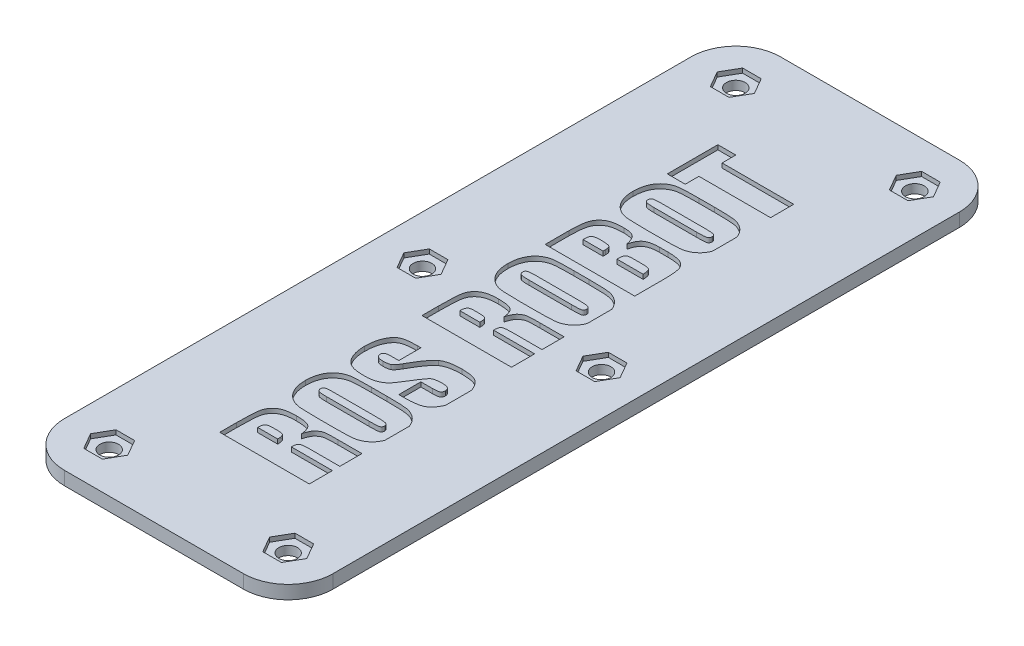
SolidWorks part; units mm, degrees
ref_plane "Front Plane" through (0, 0, 0) normal (0, 0, 1) x (1, 0, 0)
ref_plane "Top Plane" through (0, 0, 0) normal (0, 1, 0) x (1, 0, 0)
ref_plane "Right Plane" through (0, 0, 0) normal (1, 0, 0) x (0, 0, -1)
sketch "Sketch1" plane through (0, 0, 0) normal (0, 1, 0) x (1, 0, 0)
  line L1 (-30, 80) -> (30, 80)
  line L2 (-30, 80) -> (-30, -80)
  line L3 (-30, -80) -> (30, -80)
  line L4 (30, 80) -> (30, -80)
  line L5 (-30, 80) -> (30, -80) construction
  line L6 (-30, -80) -> (30, 80) construction
  point P0 (0, 0)
  dimension "D1" = 60
  dimension "D2" = 160
extrude "Boss-Extrude1" add sketch "Sketch1" along normal blind 3
sketch "Sketch2" plane through (0, 3, 0) normal (0, 1, 0) x (1, 0, 0)
  line L0 (-30, -80) -> (30, -80) construction
  line L2 (-30, 80) -> (-30, -80) construction
  circle A0 centre (-20, -70) radius 2.09
  circle A1 centre (-20, 0) radius 2.09
  circle A2 centre (-20, 70) radius 2.09
  dimension "D1" = 4.18
  dimension "D2" = 70
  dimension "D3" = 70
  dimension "D4" = 10
  dimension "D5" = 10
extrude "Cut-Extrude1" cut sketch "Sketch2" against normal through all
mirror "Mirror1" about plane through (0, 0, 0) normal (1, 0, 0) of "Cut-Extrude1"
sketch "Sketch3" plane through (0, 3, 0) normal (0, 1, 0) x (1, 0, 0)
  line L0 (10, -60) -> (10, 60)
  line L1 (-30, 80) -> (-30, -80) construction
  line L2 (-10, -55.2941) -> (-10, -51.5662)
  line L3 (4.6581, -43.5294) -> (10, -43.5294)
  line L4 (10, -43.5294) -> (10, -48.4706)
  line L5 (10, -48.4706) -> (3.2353, -48.4706)
  line L6 (0.8235, -50.1176) -> (10, -50.1176)
  line L7 (10, -50.1176) -> (10, -55.2941)
  line L8 (10, -55.2941) -> (-10, -55.2941)
  line L9 (-6.7059, -50.1176) -> (-2.2353, -50.1176)
  line L10 (-4.0478, -48.4706) -> (-5.1544, -48.4706)
  line L11 (1.7206, -41.6471) -> (-1.7206, -41.6471)
  line L12 (-1.7206, -29.6471) -> (1.7206, -29.6471)
  line L13 (-4.9596, -36.4706) -> (4.5662, -36.4706)
  line L14 (4.4154, -34.8235) -> (-4.9596, -34.8235)
  line L15 (-3.8824, -16.4706) -> (-3.8824, -21.4118)
  line L16 (-3.8824, -21.4118) -> (-5.4632, -21.4118)
  line L17 (4.0478, -28) -> (2.7059, -28)
  line L18 (2.7059, -28) -> (2.7059, -23.0588)
  line L19 (2.7059, -23.0588) -> (5.2978, -23.0588)
  line L20 (-4.6875, -16.4706) -> (-3.8824, -16.4706)
  line L21 (-10, -10.1176) -> (-10, -6.3897)
  line L22 (4.6581, 1.6471) -> (10, 1.6471)
  line L23 (10, 1.6471) -> (10, -3.2941)
  line L24 (10, -3.2941) -> (3.2353, -3.2941)
  line L25 (0.8235, -4.9412) -> (10, -4.9412)
  line L26 (10, -4.9412) -> (10, -10.1176)
  line L27 (10, -10.1176) -> (-10, -10.1176)
  line L28 (-6.7059, -4.9412) -> (-2.2353, -4.9412)
  line L29 (-4.0478, -3.2941) -> (-5.1544, -3.2941)
  line L30 (1.7206, 3.5294) -> (-1.7206, 3.5294)
  line L31 (-1.7206, 15.5294) -> (1.7206, 15.5294)
  line L32 (-4.9596, 8.7059) -> (4.5662, 8.7059)
  line L33 (4.4154, 10.3529) -> (-4.9596, 10.3529)
  line L34 (-10, 17.4118) -> (-10, 22.7169)
  line L35 (3.364, 29.6471) -> (5.2426, 29.6471)
  line L36 (10, 23.4926) -> (10, 17.4118)
  line L37 (10, 17.4118) -> (-10, 17.4118)
  line L38 (-6.7059, 22.5882) -> (-2.2353, 22.5882)
  line L39 (0.8235, 22.5882) -> (6.7059, 22.5882)
  line L40 (4.7463, 24.4706) -> (2.7831, 24.4706)
  line L41 (1.7206, 31.5294) -> (-1.7206, 31.5294)
  line L42 (-1.7206, 43.5294) -> (1.7206, 43.5294)
  line L43 (-4.9596, 36.7059) -> (4.5662, 36.7059)
  line L44 (4.4154, 38.3529) -> (-4.9596, 38.3529)
  line L45 (-10, 56) -> (-6, 56)
  line L46 (-6, 56) -> (-6, 52.9412)
  line L47 (-6, 52.9412) -> (10, 52.9412)
  line L48 (10, 52.9412) -> (10, 47.7647)
  line L49 (10, 47.7647) -> (-6, 47.7647)
  line L50 (-6, 47.7647) -> (-6, 44.7059)
  line L51 (-6, 44.7059) -> (-10, 44.7059)
  line L52 (-10, 44.7059) -> (-10, 56)
  spline S0 degree 3 poles (-10, -51.5662) (-10.0021, -50.9938) (-9.9925, -50.1738) (-9.9618, -49.131) (-9.9343, -48.4616) (-9.8938, -47.8671) (-9.8469, -47.3485) (-9.7938, -46.9053) (-9.7279, -46.5265) (-9.6422, -46.1927) (-9.5296, -45.8846) (-9.3956, -45.5898) (-9.2282, -45.3117) (-9.0316, -45.0523) (-8.8156, -44.8023) (-8.5646, -44.5748) (-8.2904, -44.3559) (-7.9777, -44.158) (-7.6226, -43.9907) (-7.2263, -43.847) (-6.7869, -43.7305) (-6.3051, -43.6403) (-5.579, -43.5478) (-5.0099, -43.5348) (-4.6176, -43.5294) knots 0 0 0 0 0.148881 0.213303 0.271377 0.323138 0.368276 0.406827 0.439217 0.468212 0.496346 0.524443 0.552325 0.580569 0.609028 0.638128 0.668547 0.700209 0.734143 0.770448 0.80973 0.852244 0.897872 1 1 1 1
  spline S1 degree 3 poles (-4.6176, -43.5294) (-4.2653, -43.5236) (-3.7599, -43.5474) (-3.1182, -43.6025) (-2.7075, -43.671) (-2.3432, -43.7491) (-2.0238, -43.8459) (-1.7543, -43.9676) (-1.5246, -44.1057) (-1.3304, -44.2743) (-1.1605, -44.4757) (-1.0104, -44.7121) (-0.8806, -44.9835) (-0.7776, -45.291) (-0.6464, -45.7633) (-0.5975, -46.1443) (-0.5735, -46.4081) knots 0 0 0 0 0.183844 0.264214 0.336185 0.401092 0.458783 0.510057 0.555172 0.598283 0.643683 0.692329 0.744143 0.800414 0.861431 1 1 1 1
  spline S2 degree 3 poles (-0.5735, -46.4081) (-0.5082, -46.1692) (-0.4158, -45.8227) (-0.2536, -45.3924) (-0.1242, -45.1174) (0.0082, -44.8722) (0.1462, -44.6567) (0.2982, -44.4752) (0.5056, -44.2791) (0.7695, -44.0853) (1.0739, -43.8901) (1.3668, -43.7472) (1.6163, -43.6653) (1.8438, -43.6284) (2.0703, -43.5981) (2.3577, -43.579) (2.7033, -43.5604) (3.1078, -43.5466) (3.7658, -43.5296) (4.2893, -43.5348) (4.6581, -43.5294) knots 0 0 0 0 0.11021 0.159198 0.204304 0.245276 0.283065 0.317885 0.350264 0.409778 0.463156 0.510931 0.554366 0.579275 0.613344 0.655979 0.70728 0.767268 0.835956 1 1 1 1
  spline S3 degree 3 poles (3.2353, -48.4706) (2.989, -48.4726) (2.6391, -48.4726) (2.1993, -48.5048) (1.9269, -48.5332) (1.6924, -48.5693) (1.4957, -48.6105) (1.339, -48.6657) (1.2146, -48.7289) (1.114, -48.8112) (1.0393, -48.9233) (0.9667, -49.0542) (0.9194, -49.2179) (0.8733, -49.4037) (0.8356, -49.7073) (0.824, -49.9481) (0.8235, -50.1176) knots 0 0 0 0 0.208735 0.296167 0.373443 0.440695 0.497113 0.543415 0.581035 0.614932 0.652106 0.694368 0.741317 0.795712 0.856499 1 1 1 1
  spline S4 degree 3 poles (-2.2353, -50.1176) (-2.241, -49.859) (-2.2449, -49.4942) (-2.3595, -49.0703) (-2.4455, -48.8674) (-2.5571, -48.7457) (-2.6702, -48.6674) (-2.8204, -48.6082) (-3.0015, -48.5571) (-3.2158, -48.5182) (-3.5672, -48.4758) (-3.8494, -48.4762) (-4.0478, -48.4706) knots 0 0 0 0 0.26299 0.361623 0.442867 0.481356 0.526611 0.580322 0.643299 0.716254 0.799641 1 1 1 1
  spline S5 degree 3 poles (-5.1544, -48.4706) (-5.4183, -48.4732) (-5.7882, -48.4915) (-6.209, -48.649) (-6.422, -48.8134) (-6.5523, -49.0502) (-6.6913, -49.4796) (-6.7008, -49.8538) (-6.7059, -50.1176) knots 0 0 0 0 0.296724 0.405999 0.497474 0.590179 0.702697 1 1 1 1
  spline S6 degree 3 poles (1.7206, -29.6471) (2.1887, -29.6516) (2.8628, -29.6489) (3.7244, -29.6629) (4.2868, -29.6838) (4.7956, -29.6992) (5.249, -29.7256) (5.6474, -29.7548) (6.1016, -29.7961) (6.625, -29.8819) (7.2194, -30.0688) (7.7848, -30.3319) (8.3184, -30.6676) (8.8126, -31.0692) (9.2459, -31.5466) (9.6203, -32.0876) (9.9272, -32.6949) (10.1748, -33.3563) (10.4086, -34.3407) (10.4749, -35.116) (10.4706, -35.6471) knots 0 0 0 0 0.113101 0.162848 0.208171 0.249056 0.285827 0.31789 0.345554 0.396029 0.44566 0.495598 0.546282 0.597611 0.648955 0.701516 0.75607 0.812935 0.871747 1 1 1 1
  spline S7 degree 3 poles (10.4706, -35.6471) (10.4702, -36.1567) (10.4117, -36.9073) (10.1869, -37.8648) (9.9551, -38.5228) (9.666, -39.1346) (9.2939, -39.6787) (8.8684, -40.1717) (8.3693, -40.5862) (7.8326, -40.9353) (7.2648, -41.2061) (6.6744, -41.4) (6.1562, -41.4954) (5.705, -41.5355) (5.3079, -41.5652) (4.8519, -41.59) (4.3384, -41.6129) (3.766, -41.6259) (2.8873, -41.6415) (2.1985, -41.6458) (1.7206, -41.6471) knots 0 0 0 0 0.123187 0.181008 0.237203 0.291505 0.343988 0.396026 0.44835 0.500181 0.550382 0.599921 0.649928 0.677302 0.709372 0.746151 0.787647 0.833563 0.884505 1 1 1 1
  spline S8 degree 3 poles (-1.7206, -41.6471) (-2.1875, -41.6426) (-2.8616, -41.6453) (-3.7232, -41.6312) (-4.2868, -41.6107) (-4.7942, -41.5935) (-5.2479, -41.5731) (-5.6461, -41.5428) (-6.102, -41.5024) (-6.6245, -41.4108) (-7.2196, -41.2259) (-7.7852, -40.961) (-8.3211, -40.6288) (-8.8141, -40.2235) (-9.2437, -39.7445) (-9.6213, -39.2061) (-9.9283, -38.5999) (-10.1693, -37.9353) (-10.4131, -36.9536) (-10.4652, -36.1757) (-10.4706, -35.6471) knots 0 0 0 0 0.112808 0.162853 0.208178 0.249064 0.285525 0.317884 0.345549 0.396077 0.445709 0.495649 0.546586 0.597688 0.649252 0.701572 0.756128 0.812892 0.872063 1 1 1 1
  spline S9 degree 3 poles (-10.4706, -35.6471) (-10.4714, -35.1372) (-10.4096, -34.3888) (-10.1907, -33.4315) (-9.9597, -32.7739) (-9.664, -32.1639) (-9.2966, -31.6157) (-8.8667, -31.1263) (-8.3697, -30.7111) (-7.8316, -30.3634) (-7.2658, -30.087) (-6.6754, -29.8952) (-6.1588, -29.7978) (-5.7072, -29.7597) (-5.3094, -29.7227) (-4.8517, -29.7062) (-4.3385, -29.6803) (-3.7659, -29.6698) (-2.8875, -29.6434) (-2.1984, -29.6546) (-1.7206, -29.6471) knots 0 0 0 0 0.123194 0.180663 0.236861 0.291296 0.344027 0.395847 0.448174 0.500008 0.55034 0.599882 0.649601 0.676977 0.709367 0.746132 0.787631 0.833549 0.884501 1 1 1 1
  spline S10 degree 3 poles (-4.9596, -34.8235) (-5.1753, -34.8242) (-5.4829, -34.83) (-5.8716, -34.843) (-6.1155, -34.8622) (-6.3276, -34.8839) (-6.5086, -34.9074) (-6.6559, -34.9406) (-6.806, -34.9862) (-6.954, -35.0702) (-7.1431, -35.2687) (-7.1725, -35.486) (-7.1765, -35.6213) knots 0 0 0 0 0.245382 0.350014 0.44228 0.523563 0.592561 0.649714 0.69512 0.770679 0.840726 1 1 1 1
  spline S11 degree 3 poles (-7.1765, -35.6213) (-7.1826, -35.7474) (-7.1389, -35.933) (-7.0007, -36.1393) (-6.8803, -36.2454) (-6.7481, -36.3134) (-6.606, -36.3546) (-6.4264, -36.3903) (-6.2075, -36.4176) (-5.9516, -36.4453) (-5.5307, -36.4612) (-5.1963, -36.473) (-4.9596, -36.4706) knots 0 0 0 0 0.14123 0.20787 0.277368 0.319365 0.374393 0.44345 0.525667 0.62281 0.733417 1 1 1 1
  spline S12 degree 3 poles (4.5662, -36.4706) (4.8346, -36.4661) (5.2158, -36.4689) (5.6951, -36.4552) (5.9902, -36.4341) (6.2432, -36.4194) (6.4541, -36.3928) (6.6225, -36.365) (6.7864, -36.3252) (6.9456, -36.2427) (7.1431, -36.032) (7.1757, -35.8027) (7.1765, -35.6581) knots 0 0 0 0 0.263966 0.37491 0.47152 0.554902 0.624119 0.680394 0.722784 0.789642 0.853612 1 1 1 1
  spline S13 degree 3 poles (7.1765, -35.6581) (7.1748, -35.5096) (7.1356, -35.267) (6.9074, -35.0588) (6.7277, -34.9785) (6.5458, -34.9318) (6.3632, -34.9057) (6.1401, -34.8796) (5.8753, -34.8573) (5.5687, -34.8447) (5.0773, -34.8286) (4.6887, -34.825) (4.4154, -34.8235) knots 0 0 0 0 0.144509 0.209626 0.282207 0.327425 0.385695 0.455209 0.538352 0.635125 0.743353 1 1 1 1
  spline S14 degree 3 poles (-5.4632, -21.4118) (-5.765, -21.4118) (-6.1723, -21.4209) (-6.6458, -21.5046) (-6.8672, -21.593) (-7.0158, -21.7183) (-7.1437, -21.9403) (-7.1819, -22.1356) (-7.1765, -22.2721) knots 0 0 0 0 0.412531 0.554325 0.654756 0.734266 0.814634 1 1 1 1
  spline S15 degree 3 poles (-7.1765, -22.2721) (-7.1753, -22.4224) (-7.1339, -22.6526) (-6.9564, -22.8986) (-6.7779, -23.0494) (-6.5473, -23.1638) (-6.1427, -23.267) (-5.8109, -23.3007) (-5.5735, -23.2941) knots 0 0 0 0 0.212113 0.312859 0.418563 0.535756 0.66915 1 1 1 1
  spline S16 degree 3 poles (-5.5735, -23.2941) (-5.2685, -23.2963) (-4.7355, -23.2666) (-4.2139, -23.1434) (-4.0074, -23.0441) knots 0 0 0 0 0.572651 1 1 1 1
  spline S17 degree 3 poles (-4.0074, -23.0441) (-3.9087, -22.9953) (-3.7635, -22.892) (-3.5783, -22.7165) (-3.4317, -22.5391) (-3.2741, -22.3344) (-3.0492, -21.9996) (-2.8928, -21.7223) (-2.7831, -21.5294) knots 0 0 0 0 0.166753 0.269572 0.387216 0.516182 0.662459 1 1 1 1
  spline S18 degree 3 poles (-2.7831, -21.5294) (-2.4734, -20.9703) (-2.0184, -20.1729) (-1.3881, -19.1897) (-0.9563, -18.5738) (-0.5522, -18.0389) (-0.0677, -17.4805) (0.3024, -17.1194) (0.5662, -16.9375) knots 0 0 0 0 0.335278 0.4813 0.612364 0.729739 0.832713 1 1 1 1
  spline S19 degree 3 poles (0.5662, -16.9375) (0.806, -16.77) (1.2115, -16.5589) (1.8106, -16.3573) (2.3243, -16.226) (2.8906, -16.1237) (3.7446, -16.0244) (4.4137, -16) (4.875, -16) knots 0 0 0 0 0.195997 0.304678 0.423526 0.551406 0.690506 1 1 1 1
  spline S20 degree 3 poles (4.875, -16) (5.2122, -15.9983) (5.6998, -16.0135) (6.3256, -16.0701) (6.7422, -16.1221) (7.1236, -16.1969) (7.469, -16.2838) (7.7801, -16.385) (8.0583, -16.5087) (8.3139, -16.656) (8.557, -16.8277) (8.7858, -17.0338) (9.0067, -17.2654) (9.2179, -17.528) (9.4131, -17.8237) (9.6079, -18.1433) (9.8414, -18.6198) (10.1006, -19.2594) (10.3969, -20.3943) (10.4676, -21.2925) (10.4706, -21.9044) knots 0 0 0 0 0.107325 0.155097 0.199939 0.240858 0.278693 0.313224 0.344823 0.375395 0.406993 0.439316 0.473245 0.508753 0.546395 0.585923 0.627781 0.715119 0.805079 1 1 1 1
  spline S21 degree 3 poles (10.4706, -21.9044) (10.4757, -22.2484) (10.4446, -22.7548) (10.3628, -23.4141) (10.2732, -23.8804) (10.1612, -24.328) (10.0192, -24.7555) (9.8605, -25.1658) (9.6676, -25.5494) (9.4591, -25.9093) (9.2368, -26.2396) (8.9991, -26.5368) (8.7496, -26.8027) (8.4841, -27.0361) (8.2022, -27.235) (7.9096, -27.4062) (7.5968, -27.5388) (7.2633, -27.6501) (6.9011, -27.7452) (6.505, -27.82) (6.0773, -27.8875) (5.616, -27.9373) (4.936, -27.9878) (4.4094, -27.9998) (4.0478, -28) knots 0 0 0 0 0.100148 0.147671 0.19347 0.238417 0.282003 0.324638 0.366476 0.406958 0.44578 0.482362 0.517724 0.551885 0.585175 0.618127 0.650431 0.683967 0.720516 0.759451 0.801367 0.846634 0.894615 1 1 1 1
  spline S22 degree 3 poles (5.2978, -23.0588) (5.4794, -23.0613) (5.7378, -23.049) (6.0657, -23.0335) (6.2711, -23.0047) (6.4517, -22.98) (6.6031, -22.9371) (6.7301, -22.8953) (6.8628, -22.8277) (6.9937, -22.7117) (7.1506, -22.4544) (7.1729, -22.2151) (7.1765, -22.0551) knots 0 0 0 0 0.221449 0.31586 0.400263 0.474516 0.538003 0.591926 0.637412 0.719013 0.801608 1 1 1 1
  spline S23 degree 3 poles (7.1765, -22.0551) (7.1797, -21.8865) (7.1319, -21.6346) (6.944, -21.3618) (6.7516, -21.2047) (6.511, -21.0827) (6.094, -20.9668) (5.75, -20.942) (5.5074, -20.9412) knots 0 0 0 0 0.223439 0.325747 0.431377 0.547858 0.679404 1 1 1 1
  spline S24 degree 3 poles (5.5074, -20.9412) (5.2301, -20.9407) (4.8335, -20.9536) (4.3315, -21.0008) (4.0144, -21.0585) (3.7334, -21.12) (3.4321, -21.228) (3.2311, -21.3302) (3.125, -21.4228) knots 0 0 0 0 0.33668 0.481833 0.611779 0.728037 0.830669 1 1 1 1
  spline S25 degree 3 poles (3.125, -21.4228) (3.0067, -21.5278) (2.832, -21.7237) (2.5986, -22.0274) (2.3862, -22.3232) (2.1458, -22.6637) (1.7857, -23.219) (1.5142, -23.6656) (1.3235, -23.9779) knots 0 0 0 0 0.151179 0.250673 0.366592 0.499698 0.649697 1 1 1 1
  spline S26 degree 3 poles (1.3235, -23.9779) (1.1312, -24.2944) (0.8539, -24.7471) (0.4867, -25.3154) (0.2465, -25.6779) (0.024, -25.9952) (-0.1732, -26.2708) (-0.3489, -26.5042) (-0.5602, -26.7562) (-0.8385, -27.0321) (-1.2198, -27.322) (-1.6571, -27.5826) (-2.1499, -27.8167) (-2.7079, -28.0109) (-3.5918, -28.187) (-4.2954, -28.2419) (-4.7868, -28.2353) knots 0 0 0 0 0.139506 0.199942 0.254867 0.303273 0.345934 0.382495 0.413289 0.469759 0.52968 0.593251 0.661185 0.734906 0.815121 1 1 1 1
  spline S27 degree 3 poles (-4.7868, -28.2353) (-5.1483, -28.2299) (-5.6721, -28.2229) (-6.342, -28.1555) (-6.7866, -28.0911) (-7.1929, -28.0062) (-7.5618, -27.9063) (-7.8893, -27.7803) (-8.183, -27.6392) (-8.4486, -27.4744) (-8.6932, -27.2854) (-8.9296, -27.0793) (-9.1431, -26.8428) (-9.3479, -26.5869) (-9.5388, -26.3089) (-9.711, -26.0053) (-9.9259, -25.5665) (-10.1466, -24.9651) (-10.4114, -23.8851) (-10.4702, -23.0241) (-10.4706, -22.4338) knots 0 0 0 0 0.115094 0.16642 0.214115 0.25793 0.298418 0.335563 0.369391 0.401957 0.434786 0.46765 0.501588 0.535991 0.571894 0.608743 0.64693 0.727243 0.81197 1 1 1 1
  spline S28 degree 3 poles (-10.4706, -22.4338) (-10.4681, -22.0991) (-10.4534, -21.6059) (-10.3832, -20.9641) (-10.3105, -20.511) (-10.2136, -20.0772) (-10.102, -19.6612) (-9.9641, -19.2668) (-9.8111, -18.8916) (-9.6395, -18.5421) (-9.457, -18.2203) (-9.2585, -17.9336) (-9.0613, -17.6686) (-8.8392, -17.446) (-8.617, -17.2428) (-8.377, -17.0786) (-8.1223, -16.9405) (-7.8384, -16.8309) (-7.5198, -16.7307) (-7.1549, -16.6529) (-6.7482, -16.5815) (-6.2949, -16.5328) (-5.6039, -16.4819) (-5.0626, -16.471) (-4.6875, -16.4706) knots 0 0 0 0 0.103075 0.151642 0.198646 0.244222 0.288419 0.331123 0.37273 0.413047 0.450895 0.486465 0.520341 0.552351 0.583079 0.612899 0.641587 0.672056 0.706415 0.744299 0.786776 0.83347 0.88453 1 1 1 1
  spline S29 degree 3 poles (-10, -6.3897) (-10.0021, -5.8173) (-9.9925, -4.9973) (-9.9618, -3.9545) (-9.9343, -3.2851) (-9.8938, -2.6907) (-9.8469, -2.172) (-9.7938, -1.7288) (-9.7279, -1.3501) (-9.6422, -1.0162) (-9.5296, -0.7081) (-9.3956, -0.4133) (-9.2282, -0.1353) (-9.0316, 0.1241) (-8.8156, 0.3741) (-8.5646, 0.6016) (-8.2904, 0.8205) (-7.9777, 1.0184) (-7.6226, 1.1858) (-7.2263, 1.3294) (-6.7869, 1.4459) (-6.3051, 1.5362) (-5.579, 1.6287) (-5.0099, 1.6416) (-4.6176, 1.6471) knots 0 0 0 0 0.148881 0.213303 0.271377 0.323138 0.368276 0.406827 0.439217 0.468212 0.496346 0.524443 0.552325 0.580569 0.609028 0.638128 0.668547 0.700209 0.734143 0.770448 0.80973 0.852244 0.897872 1 1 1 1
  spline S30 degree 3 poles (-4.6176, 1.6471) (-4.2653, 1.6529) (-3.7599, 1.629) (-3.1182, 1.574) (-2.7075, 1.5055) (-2.3432, 1.4273) (-2.0238, 1.3305) (-1.7543, 1.2089) (-1.5246, 1.0707) (-1.3304, 0.9022) (-1.1605, 0.7008) (-1.0104, 0.4644) (-0.8806, 0.1929) (-0.7776, -0.1145) (-0.6464, -0.5869) (-0.5975, -0.9678) (-0.5735, -1.2316) knots 0 0 0 0 0.183844 0.264214 0.336185 0.401092 0.458783 0.510057 0.555172 0.598283 0.643683 0.692329 0.744143 0.800414 0.861431 1 1 1 1
  spline S31 degree 3 poles (-0.5735, -1.2316) (-0.5082, -0.9927) (-0.4158, -0.6463) (-0.2536, -0.216) (-0.1242, 0.0591) (0.0082, 0.3043) (0.1462, 0.5197) (0.2982, 0.7013) (0.5056, 0.8974) (0.7695, 1.0911) (1.0739, 1.2863) (1.3668, 1.4293) (1.6163, 1.5112) (1.8438, 1.5481) (2.0703, 1.5783) (2.3577, 1.5974) (2.7033, 1.6161) (3.1078, 1.6299) (3.7658, 1.6469) (4.2893, 1.6416) (4.6581, 1.6471) knots 0 0 0 0 0.11021 0.159198 0.204304 0.245276 0.283065 0.317885 0.350264 0.409778 0.463156 0.510931 0.554366 0.579275 0.613344 0.655979 0.70728 0.767268 0.835956 1 1 1 1
  spline S32 degree 3 poles (3.2353, -3.2941) (2.989, -3.2962) (2.6391, -3.2961) (2.1993, -3.3283) (1.9269, -3.3567) (1.6924, -3.3928) (1.4957, -3.4341) (1.339, -3.4893) (1.2146, -3.5525) (1.114, -3.6348) (1.0393, -3.7469) (0.9667, -3.8778) (0.9194, -4.0414) (0.8733, -4.2272) (0.8356, -4.5308) (0.824, -4.7717) (0.8235, -4.9412) knots 0 0 0 0 0.208735 0.296167 0.373443 0.440695 0.497113 0.543415 0.581035 0.614932 0.652106 0.694368 0.741317 0.795712 0.856499 1 1 1 1
  spline S33 degree 3 poles (-2.2353, -4.9412) (-2.241, -4.6826) (-2.2449, -4.3177) (-2.3595, -3.8938) (-2.4455, -3.6909) (-2.5571, -3.5692) (-2.6702, -3.491) (-2.8204, -3.4317) (-3.0015, -3.3807) (-3.2158, -3.3417) (-3.5672, -3.2993) (-3.8494, -3.2997) (-4.0478, -3.2941) knots 0 0 0 0 0.26299 0.361623 0.442867 0.481356 0.526611 0.580322 0.643299 0.716254 0.799641 1 1 1 1
  spline S34 degree 3 poles (-5.1544, -3.2941) (-5.4183, -3.2968) (-5.7882, -3.315) (-6.209, -3.4725) (-6.422, -3.6369) (-6.5523, -3.8737) (-6.6913, -4.3032) (-6.7008, -4.6773) (-6.7059, -4.9412) knots 0 0 0 0 0.296724 0.405999 0.497474 0.590179 0.702697 1 1 1 1
  spline S35 degree 3 poles (1.7206, 15.5294) (2.1887, 15.5249) (2.8628, 15.5276) (3.7244, 15.5136) (4.2868, 15.4926) (4.7956, 15.4773) (5.249, 15.4509) (5.6474, 15.4217) (6.1016, 15.3804) (6.625, 15.2946) (7.2194, 15.1077) (7.7848, 14.8446) (8.3184, 14.5089) (8.8126, 14.1073) (9.2459, 13.6298) (9.6203, 13.0889) (9.9272, 12.4816) (10.1748, 11.8202) (10.4086, 10.8357) (10.4749, 10.0605) (10.4706, 9.5294) knots 0 0 0 0 0.113101 0.162848 0.208171 0.249056 0.285827 0.31789 0.345554 0.396029 0.44566 0.495598 0.546282 0.597611 0.648955 0.701516 0.75607 0.812935 0.871747 1 1 1 1
  spline S36 degree 3 poles (10.4706, 9.5294) (10.4702, 9.0198) (10.4117, 8.2692) (10.1869, 7.3116) (9.9551, 6.6537) (9.666, 6.0419) (9.2939, 5.4977) (8.8684, 5.0048) (8.3693, 4.5903) (7.8326, 4.2412) (7.2648, 3.9704) (6.6744, 3.7764) (6.1562, 3.681) (5.705, 3.6409) (5.3079, 3.6113) (4.8519, 3.5865) (4.3384, 3.5636) (3.766, 3.5505) (2.8873, 3.535) (2.1985, 3.5307) (1.7206, 3.5294) knots 0 0 0 0 0.123187 0.181008 0.237203 0.291505 0.343988 0.396026 0.44835 0.500181 0.550382 0.599921 0.649928 0.677302 0.709372 0.746151 0.787647 0.833563 0.884505 1 1 1 1
  spline S37 degree 3 poles (-1.7206, 3.5294) (-2.1875, 3.5339) (-2.8616, 3.5312) (-3.7232, 3.5453) (-4.2868, 3.5657) (-4.7942, 3.5829) (-5.2479, 3.6034) (-5.6461, 3.6337) (-6.102, 3.674) (-6.6245, 3.7656) (-7.2196, 3.9505) (-7.7852, 4.2155) (-8.3211, 4.5477) (-8.8141, 4.953) (-9.2437, 5.432) (-9.6213, 5.9703) (-9.9283, 6.5765) (-10.1693, 7.2411) (-10.4131, 8.2229) (-10.4652, 9.0008) (-10.4706, 9.5294) knots 0 0 0 0 0.112808 0.162853 0.208178 0.249064 0.285525 0.317884 0.345549 0.396077 0.445709 0.495649 0.546586 0.597688 0.649252 0.701572 0.756128 0.812892 0.872063 1 1 1 1
  spline S38 degree 3 poles (-10.4706, 9.5294) (-10.4714, 10.0393) (-10.4096, 10.7877) (-10.1907, 11.7449) (-9.9597, 12.4026) (-9.664, 13.0126) (-9.2966, 13.5607) (-8.8667, 14.0501) (-8.3697, 14.4654) (-7.8316, 14.813) (-7.2658, 15.0895) (-6.6754, 15.2813) (-6.1588, 15.3787) (-5.7072, 15.4167) (-5.3094, 15.4538) (-4.8517, 15.4703) (-4.3385, 15.4962) (-3.7659, 15.5067) (-2.8875, 15.5331) (-2.1984, 15.5218) (-1.7206, 15.5294) knots 0 0 0 0 0.123194 0.180663 0.236861 0.291296 0.344027 0.395847 0.448174 0.500008 0.55034 0.599882 0.649601 0.676977 0.709367 0.746132 0.787631 0.833549 0.884501 1 1 1 1
  spline S39 degree 3 poles (-4.9596, 10.3529) (-5.1753, 10.3523) (-5.4829, 10.3464) (-5.8716, 10.3334) (-6.1155, 10.3143) (-6.3276, 10.2926) (-6.5086, 10.2691) (-6.6559, 10.2359) (-6.806, 10.1902) (-6.954, 10.1063) (-7.1431, 9.9078) (-7.1725, 9.6905) (-7.1765, 9.5551) knots 0 0 0 0 0.245382 0.350014 0.44228 0.523563 0.592561 0.649714 0.69512 0.770679 0.840726 1 1 1 1
  spline S40 degree 3 poles (-7.1765, 9.5551) (-7.1826, 9.4291) (-7.1389, 9.2435) (-7.0007, 9.0372) (-6.8803, 8.931) (-6.7481, 8.8631) (-6.606, 8.8219) (-6.4264, 8.7862) (-6.2075, 8.7588) (-5.9516, 8.7312) (-5.5307, 8.7153) (-5.1963, 8.7035) (-4.9596, 8.7059) knots 0 0 0 0 0.14123 0.20787 0.277368 0.319365 0.374393 0.44345 0.525667 0.62281 0.733417 1 1 1 1
  spline S41 degree 3 poles (4.5662, 8.7059) (4.8346, 8.7104) (5.2158, 8.7076) (5.6951, 8.7213) (5.9902, 8.7424) (6.2432, 8.7571) (6.4541, 8.7836) (6.6225, 8.8115) (6.7864, 8.8513) (6.9456, 8.9338) (7.1431, 9.1444) (7.1757, 9.3737) (7.1765, 9.5184) knots 0 0 0 0 0.263966 0.37491 0.47152 0.554902 0.624119 0.680394 0.722784 0.789642 0.853612 1 1 1 1
  spline S42 degree 3 poles (7.1765, 9.5184) (7.1748, 9.6669) (7.1356, 9.9095) (6.9074, 10.1176) (6.7277, 10.198) (6.5458, 10.2447) (6.3632, 10.2708) (6.1401, 10.2969) (5.8753, 10.3191) (5.5687, 10.3318) (5.0773, 10.3479) (4.6887, 10.3515) (4.4154, 10.3529) knots 0 0 0 0 0.144509 0.209626 0.282207 0.327425 0.385695 0.455209 0.538352 0.635125 0.743353 1 1 1 1
  spline S43 degree 3 poles (-10, 22.7169) (-9.9955, 23.1103) (-9.9921, 23.6819) (-9.9527, 24.4186) (-9.9071, 24.9135) (-9.857, 25.3711) (-9.7961, 25.7911) (-9.7188, 26.1725) (-9.6309, 26.5207) (-9.5237, 26.8424) (-9.3912, 27.1434) (-9.2355, 27.4283) (-9.0587, 27.6987) (-8.8552, 27.9531) (-8.6276, 28.1917) (-8.375, 28.4137) (-8.0977, 28.6217) (-7.7862, 28.8126) (-7.4301, 28.9734) (-7.0293, 29.1081) (-6.5873, 29.2218) (-6.1, 29.3043) (-5.3665, 29.3894) (-4.791, 29.4161) (-4.3934, 29.4118) knots 0 0 0 0 0.114375 0.166108 0.21439 0.258844 0.299904 0.337701 0.371916 0.404248 0.43615 0.467396 0.498519 0.529953 0.561953 0.594259 0.627603 0.66261 0.70023 0.740899 0.785396 0.832777 0.884431 1 1 1 1
  spline S44 degree 3 poles (-4.3934, 29.4118) (-4.127, 29.416) (-3.7431, 29.3962) (-3.2561, 29.335) (-2.9376, 29.2799) (-2.6536, 29.1963) (-2.3989, 29.1046) (-2.1784, 28.9884) (-1.985, 28.8544) (-1.8163, 28.6891) (-1.6558, 28.4982) (-1.5162, 28.2669) (-1.3783, 28.0074) (-1.2489, 27.7134) (-1.0963, 27.2527) (-0.9938, 26.8887) (-0.9412, 26.6324) knots 0 0 0 0 0.159635 0.229972 0.294227 0.35305 0.407212 0.456169 0.502024 0.547743 0.597307 0.65111 0.709269 0.77341 0.843331 1 1 1 1
  spline S45 degree 3 poles (-0.9412, 26.6324) (-0.8783, 26.9064) (-0.7658, 27.3007) (-0.5629, 27.7876) (-0.4027, 28.1069) (-0.2205, 28.3873) (-0.0268, 28.6367) (0.1878, 28.8487) (0.4252, 29.025) (0.6872, 29.1721) (0.9755, 29.3025) (1.2968, 29.4066) (1.6481, 29.495) (2.0311, 29.565) (2.6061, 29.6282) (3.0548, 29.6461) (3.364, 29.6471) knots 0 0 0 0 0.144043 0.209309 0.269932 0.32668 0.380292 0.431325 0.480651 0.531247 0.584899 0.64245 0.703941 0.770287 0.841669 1 1 1 1
  spline S46 degree 3 poles (5.2426, 29.6471) (5.5626, 29.6468) (6.0268, 29.6352) (6.6234, 29.5846) (7.0212, 29.535) (7.3857, 29.4682) (7.7163, 29.3886) (8.0154, 29.2938) (8.3632, 29.1496) (8.7467, 28.9274) (9.131, 28.5817) (9.4335, 28.1642) (9.6212, 27.7575) (9.7292, 27.3755) (9.8021, 27.0179) (9.8619, 26.5942) (9.9131, 26.1025) (9.9518, 25.5458) (9.9944, 24.6684) (9.9944, 23.9766) (10, 23.4926) knots 0 0 0 0 0.102269 0.148253 0.191288 0.230306 0.266588 0.299901 0.330446 0.386794 0.440584 0.494395 0.550463 0.582684 0.621084 0.666995 0.719365 0.779044 0.845298 1 1 1 1
  spline S47 degree 2 poles (-2.2353, 22.5882) (-2.243, 22.875) (-2.2463, 23.1618) knots 0 0 0 1 1 1
  spline S48 degree 3 poles (-2.2463, 23.1618) (-2.2431, 23.394) (-2.2711, 23.7204) (-2.4403, 24.0836) (-2.5925, 24.231) (-2.7527, 24.3011) (-2.9141, 24.3494) (-3.1208, 24.3814) (-3.3706, 24.4159) (-3.6639, 24.4398) (-4.143, 24.4659) (-4.5245, 24.4702) (-4.7941, 24.4706) knots 0 0 0 0 0.207117 0.283923 0.350831 0.389245 0.438074 0.499907 0.574465 0.661754 0.760817 1 1 1 1
  spline S49 degree 3 poles (-4.7941, 24.4706) (-5.0622, 24.4736) (-5.4312, 24.4547) (-5.8749, 24.3777) (-6.1089, 24.2909) (-6.2879, 24.1851) (-6.4274, 24.0656) (-6.5346, 23.9321) (-6.6046, 23.7711) (-6.647, 23.5692) (-6.6936, 23.172) (-6.7017, 22.8358) (-6.7059, 22.5882) knots 0 0 0 0 0.246774 0.340005 0.413619 0.475395 0.530632 0.582131 0.631661 0.690822 0.771636 1 1 1 1
  spline S50 degree 3 poles (6.7059, 22.5882) (6.6974, 22.7721) (6.6865, 23.0359) (6.639, 23.3661) (6.6004, 23.5743) (6.5485, 23.7547) (6.4911, 23.9092) (6.4263, 24.0376) (6.3453, 24.1395) (6.2425, 24.2198) (6.117, 24.2905) (5.959, 24.3424) (5.774, 24.3915) (5.5585, 24.4261) (5.2129, 24.4608) (4.9391, 24.4751) (4.7463, 24.4706) knots 0 0 0 0 0.168584 0.241049 0.305039 0.362178 0.412572 0.455707 0.493181 0.530655 0.574326 0.624331 0.682257 0.749354 0.823771 1 1 1 1
  spline S51 degree 3 poles (2.7831, 24.4706) (2.581, 24.4703) (2.2917, 24.4675) (1.9312, 24.4278) (1.7075, 24.4033) (1.5202, 24.3573) (1.3632, 24.3087) (1.2402, 24.2464) (1.1435, 24.1736) (1.0733, 24.0756) (1.0165, 23.953) (0.9652, 23.8) (0.9227, 23.6164) (0.8865, 23.4028) (0.8455, 23.0574) (0.8306, 22.7821) (0.8235, 22.5882) knots 0 0 0 0 0.182344 0.260037 0.326886 0.384748 0.433642 0.474638 0.508444 0.541576 0.582078 0.629925 0.686713 0.751712 0.825136 1 1 1 1
  spline S52 degree 3 poles (1.7206, 43.5294) (2.1887, 43.5249) (2.8628, 43.5276) (3.7244, 43.5136) (4.2868, 43.4926) (4.7956, 43.4773) (5.249, 43.4509) (5.6474, 43.4217) (6.1016, 43.3804) (6.625, 43.2946) (7.2194, 43.1077) (7.7848, 42.8446) (8.3184, 42.5089) (8.8126, 42.1073) (9.2459, 41.6298) (9.6203, 41.0889) (9.9272, 40.4816) (10.1748, 39.8202) (10.4086, 38.8357) (10.4749, 38.0605) (10.4706, 37.5294) knots 0 0 0 0 0.113101 0.162848 0.208171 0.249056 0.285827 0.31789 0.345554 0.396029 0.44566 0.495598 0.546282 0.597611 0.648955 0.701516 0.75607 0.812935 0.871747 1 1 1 1
  spline S53 degree 3 poles (10.4706, 37.5294) (10.4702, 37.0198) (10.4117, 36.2692) (10.1869, 35.3116) (9.9551, 34.6537) (9.666, 34.0419) (9.2939, 33.4977) (8.8684, 33.0048) (8.3693, 32.5903) (7.8326, 32.2412) (7.2648, 31.9704) (6.6744, 31.7764) (6.1562, 31.681) (5.705, 31.6409) (5.3079, 31.6113) (4.8519, 31.5865) (4.3384, 31.5636) (3.766, 31.5505) (2.8873, 31.535) (2.1985, 31.5307) (1.7206, 31.5294) knots 0 0 0 0 0.123187 0.181008 0.237203 0.291505 0.343988 0.396026 0.44835 0.500181 0.550382 0.599921 0.649928 0.677302 0.709372 0.746151 0.787647 0.833563 0.884505 1 1 1 1
  spline S54 degree 3 poles (-1.7206, 31.5294) (-2.1875, 31.5339) (-2.8616, 31.5312) (-3.7232, 31.5453) (-4.2868, 31.5657) (-4.7942, 31.5829) (-5.2479, 31.6034) (-5.6461, 31.6337) (-6.102, 31.674) (-6.6245, 31.7656) (-7.2196, 31.9505) (-7.7852, 32.2155) (-8.3211, 32.5477) (-8.8141, 32.953) (-9.2437, 33.432) (-9.6213, 33.9703) (-9.9283, 34.5765) (-10.1693, 35.2411) (-10.4131, 36.2229) (-10.4652, 37.0008) (-10.4706, 37.5294) knots 0 0 0 0 0.112808 0.162853 0.208178 0.249064 0.285525 0.317884 0.345549 0.396077 0.445709 0.495649 0.546586 0.597688 0.649252 0.701572 0.756128 0.812892 0.872063 1 1 1 1
  spline S55 degree 3 poles (-10.4706, 37.5294) (-10.4714, 38.0393) (-10.4096, 38.7877) (-10.1907, 39.7449) (-9.9597, 40.4026) (-9.664, 41.0126) (-9.2966, 41.5607) (-8.8667, 42.0501) (-8.3697, 42.4654) (-7.8316, 42.813) (-7.2658, 43.0895) (-6.6754, 43.2813) (-6.1588, 43.3787) (-5.7072, 43.4167) (-5.3094, 43.4538) (-4.8517, 43.4703) (-4.3385, 43.4962) (-3.7659, 43.5067) (-2.8875, 43.5331) (-2.1984, 43.5218) (-1.7206, 43.5294) knots 0 0 0 0 0.123194 0.180663 0.236861 0.291296 0.344027 0.395847 0.448174 0.500008 0.55034 0.599882 0.649601 0.676977 0.709367 0.746132 0.787631 0.833549 0.884501 1 1 1 1
  spline S56 degree 3 poles (-4.9596, 38.3529) (-5.1753, 38.3523) (-5.4829, 38.3464) (-5.8716, 38.3334) (-6.1155, 38.3143) (-6.3276, 38.2926) (-6.5086, 38.2691) (-6.6559, 38.2359) (-6.806, 38.1902) (-6.954, 38.1063) (-7.1431, 37.9078) (-7.1725, 37.6905) (-7.1765, 37.5551) knots 0 0 0 0 0.245382 0.350014 0.44228 0.523563 0.592561 0.649714 0.69512 0.770679 0.840726 1 1 1 1
  spline S57 degree 3 poles (-7.1765, 37.5551) (-7.1826, 37.4291) (-7.1389, 37.2435) (-7.0007, 37.0372) (-6.8803, 36.931) (-6.7481, 36.8631) (-6.606, 36.8219) (-6.4264, 36.7862) (-6.2075, 36.7588) (-5.9516, 36.7312) (-5.5307, 36.7153) (-5.1963, 36.7035) (-4.9596, 36.7059) knots 0 0 0 0 0.14123 0.20787 0.277368 0.319365 0.374393 0.44345 0.525667 0.62281 0.733417 1 1 1 1
  spline S58 degree 3 poles (4.5662, 36.7059) (4.8346, 36.7104) (5.2158, 36.7076) (5.6951, 36.7213) (5.9902, 36.7424) (6.2432, 36.7571) (6.4541, 36.7836) (6.6225, 36.8115) (6.7864, 36.8513) (6.9456, 36.9338) (7.1431, 37.1444) (7.1757, 37.3737) (7.1765, 37.5184) knots 0 0 0 0 0.263966 0.37491 0.47152 0.554902 0.624119 0.680394 0.722784 0.789642 0.853612 1 1 1 1
  spline S59 degree 3 poles (7.1765, 37.5184) (7.1748, 37.6669) (7.1356, 37.9095) (6.9074, 38.1176) (6.7277, 38.198) (6.5458, 38.2447) (6.3632, 38.2708) (6.1401, 38.2969) (5.8753, 38.3191) (5.5687, 38.3318) (5.0773, 38.3479) (4.6887, 38.3515) (4.4154, 38.3529) knots 0 0 0 0 0.144509 0.209626 0.282207 0.327425 0.385695 0.455209 0.538352 0.635125 0.743353 1 1 1 1
  point P5 (-30, 0)
  point P6 (10, 0)
  dimension "D1" = 120
  dimension "D2" = 10
extrude "Cut-Extrude2" cut sketch "Sketch3" against normal blind 1 contours S3 L5 L0 L3 S2 S1 S0 L2 L8 L6 S5 L10 S4 L9 | S9 S8 L11 S7 L0 S6 L12 S13 S12 L13 S11 S10 L14 | S28 S27 S26 S25 S24 S23 S22 L19 L18 L17 S21 L0 S20 S19 S18 S17 S16 S15 S14 L16 L15 L20 | S32 L24 L0 L22 S31 S30 S29 L21 L27 L25 S34 L29 S33 L28 | S38 S37 L30 S36 L0 S35 L31 S42 S41 L32 S40 S39 L33 | S46 L35 S45 S44 S43 L34 L37 L0 S51 L40 S50 L39 S49 S48 S47 L38 | S55 S54 L41 S53 L0 S52 L42 S59 S58 L43 S57 S56 L44 | L52 L51 L50 L49 L0 L47 L46 L45 region at (-0.0506, 3, 49.6197) region at (-1.5294, 3, -50.3529) region at (6.4747, 3, -31.9872) region at (0.1248, 3, -23.1918) region at (6.4747, 3, -3.9872) region at (-0.0506, 3, 4.4433) region at (-0.0445, 3, 22.1813) region at (6.4747, 3, 41.1893)
fillet "Fillet1" radius 10 4 edges at (-30, 1.5, -80) (30, 1.5, -80) (30, 1.5, 80) (-30, 1.5, 80)
sketch "Sketch4" plane through (0, 3, 0) normal (0, 1, 0) x (1, 0, 0)
  line L0 (-20, -80) -> (20, -80) construction
  line L1 (24.1569, -70) -> (22.0785, -66.4)
  line L2 (22.0785, -66.4) -> (17.9215, -66.4)
  line L3 (17.9215, -66.4) -> (15.8431, -70)
  line L4 (15.8431, -70) -> (17.9215, -73.6)
  line L5 (17.9215, -73.6) -> (22.0785, -73.6)
  line L6 (22.0785, -73.6) -> (24.1569, -70)
  line L7 (24.1569, 0) -> (22.0785, 3.6)
  line L8 (22.0785, 3.6) -> (17.9215, 3.6)
  line L9 (17.9215, 3.6) -> (15.8431, 0)
  line L10 (15.8431, 0) -> (17.9215, -3.6)
  line L11 (17.9215, -3.6) -> (22.0785, -3.6)
  line L12 (22.0785, -3.6) -> (24.1569, 0)
  line L13 (24.1569, 70) -> (22.0785, 73.6)
  line L14 (22.0785, 73.6) -> (17.9215, 73.6)
  line L15 (17.9215, 73.6) -> (15.8431, 70)
  line L16 (15.8431, 70) -> (17.9215, 66.4)
  line L17 (17.9215, 66.4) -> (22.0785, 66.4)
  line L18 (22.0785, 66.4) -> (24.1569, 70)
  circle A0 centre (20, -70) radius 3.6 construction
  circle A1 centre (20, 0) radius 3.6 construction
  circle A2 centre (20, 70) radius 3.6 construction
  circle A3 centre (20, -70) radius 2.09 construction
  circle A4 centre (20, 0) radius 2.09 construction
  circle A5 centre (20, 70) radius 2.09 construction
  point P35 (20, -66.4)
  dimension "D1" = 7.2
extrude "Cut-Extrude3" cut sketch "Sketch4" against normal blind 1
mirror "Mirror2" about plane through (0, 0, 0) normal (1, 0, 0) of "Cut-Extrude3"
